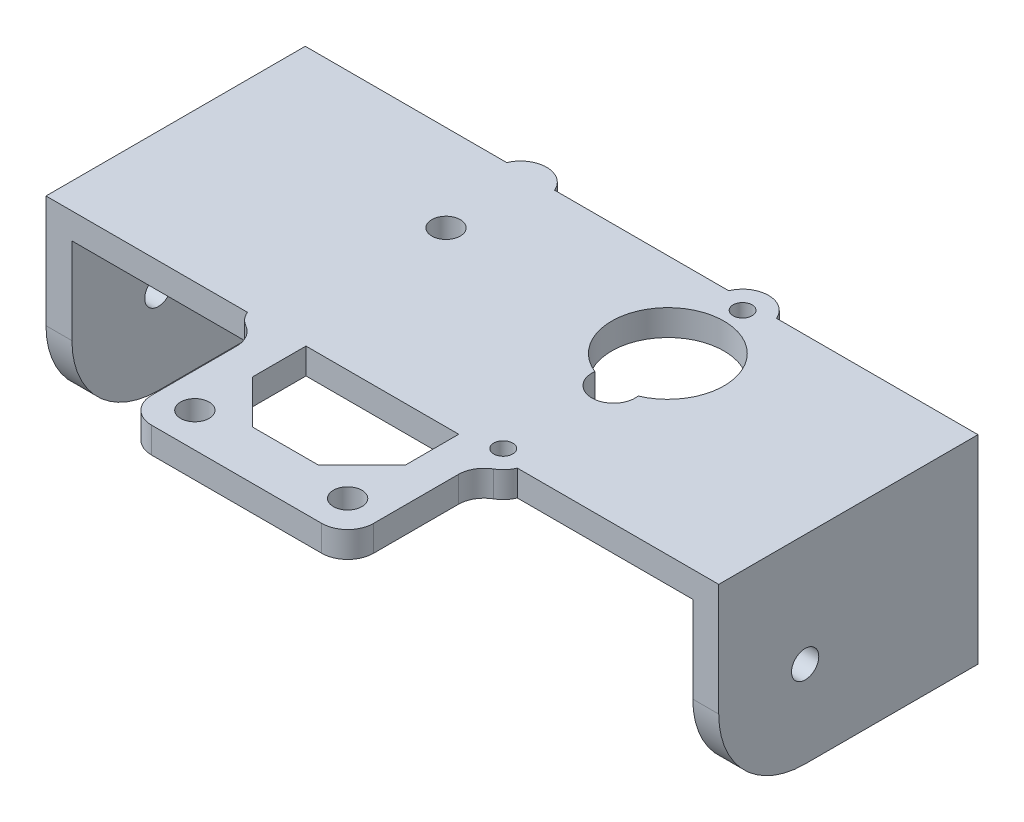
SolidWorks part; units mm, degrees
ref_plane "Front Plane" through (0, 0, 0) normal (0, 0, 1) x (1, 0, 0)
ref_plane "Top Plane" through (0, 0, 0) normal (0, 1, 0) x (1, 0, 0)
ref_plane "Right Plane" through (0, 0, 0) normal (1, 0, 0) x (0, 0, -1)
sketch "Sketch1" plane through (0, 0, 0) normal (0, 0, 1) x (1, 0, 0)
  line L0 (-32.8463, 7.5233) -> (32.9944, 7.5233) construction
  line L2 (-38.8463, 10.5233) -> (38.9944, 10.5233)
  line L3 (-38.8463, 10.5233) -> (-38.8463, 7.5233)
  line L4 (-38.8463, 7.5233) -> (38.9944, 7.5233)
  line L5 (38.9944, 10.5233) -> (38.9944, 7.5233)
  line L6 (-38.8463, 10.5233) -> (38.9944, 7.5233) construction
  line L7 (-38.8463, 7.5233) -> (38.9944, 10.5233) construction
  line L8 (38.9944, 10.5233) -> (35.9944, 10.5233)
  line L10 (-32.8463, 2.523) -> (32.9944, 2.5233) construction
  line L13 (-38.8463, 10.5233) -> (-35.8463, 10.5233)
  line L14 (-38.8463, 10.5233) -> (-38.8463, -12.4767)
  line L15 (-38.8463, -12.4767) -> (-35.8463, -12.4767)
  line L16 (-35.8463, 10.5233) -> (-35.8463, -12.4767)
  line L17 (0.0741, 2.5231) -> (0.0741, -23.3949) construction
  line L18 (38.9944, 10.5233) -> (38.9944, -12.4767)
  line L19 (38.9944, -12.4767) -> (35.9944, -12.4767)
  line L20 (35.9944, 10.5233) -> (35.9944, -12.4767)
  line L21 (-35.8463, -12.4767) -> (-32.8463, -12.4767) construction
  line L22 (32.9944, -12.4767) -> (35.9944, -12.4767) construction
  point P2 (0.2537, 9.0233)
  dimension "D1" = 3
  dimension "D2" = 3
  dimension "D3" = 3
extrude "Boss-Extrude1" add sketch "Sketch1" along normal blind 30 contours L16 L4 L14 L15 | L16 L2 L3 L4 | L20 L2 L16 L4 | L2 L20 L4 L5 | L4 L20 L19 L18 region at (-37.3463, 9.0233, 0) region at (0.0741, 9.0233, 0) region at (-37.3463, -2.4767, 0) region at (37.4944, 9.0233, 0) region at (37.4944, -2.4767, 0)
fillet "Fillet1" radius 10 2 edges at (37.4944, -12.4767, 30) (-37.3463, -12.4767, 30)
sketch "Sketch2" plane through (0, 0, 0) normal (1, 0, 0) x (0, 0, -1)
  line L0 (20, -2.4767) -> (-20, -2.4767) construction
  line L1 (-30, 10.5233) -> (-30, -2.4767) construction
  circle A0 centre (-20, -2.4767) radius 1.575
  dimension "D2" = 3.15
  dimension "D1" = 10
extrude "Cut-Extrude1" cut sketch "Sketch2" against normal mid plane 100
sketch "Sketch3" plane through (0, 10.5233, 0) normal (0, 1, 0) x (1, 0, 0)
  line L0 (0.0741, -30) -> (0, 0) construction
  line L1 (-38.8463, -30) -> (38.9944, -30) construction
  circle A2 centre (12.9136, -9.8077) radius 6.5
  circle A3 centre (12.9886, -16.1672) radius 2.5
  circle A4 centre (12.9136, -1.1577) radius 1.1
  circle A5 centre (12.9136, -28.8577) radius 1.1
  circle A6 centre (-12.508, -10.0504) radius 1.65
  dimension "D2" = 2.2
  dimension "D3" = 3.3
  dimension "D4" = 13
  dimension "D5" = 5
  dimension "D1" = 2.2
extrude "Cut-Extrude2" cut sketch "Sketch3" against normal up to surface (3 mm away) contours A5 | A2 A3 | A2 A3 | A3 A2 | A4 | A6 region at (12.9086, 10.5233, 9.3903) region at (12.976, 10.5233, 15.0994) region at (13.0009, 10.5233, 17.2105) region at (12.9136, 10.5233, 1.1577) region at (12.9136, 10.5233, 28.8577) region at (-12.508, 10.5233, 10.0504) up to face at (0.0741, 7.5233, 15)
sketch "Sketch4" plane through (0, 10.5233, 0) normal (0, 1, 0) x (1, 0, 0)
  line L0 (0.0741, -30) -> (0.0741, 0) construction
  line L1 (-38.8463, -30) -> (38.9944, -30) construction
  line L2 (-38.8463, 0) -> (38.9944, 0) construction
  line L3 (-8.7654, -36.2077) -> (-3.7654, -41.2077)
  line L4 (6.9136, -46.8577) -> (-6.7654, -46.8577)
  line L5 (-8.7654, -30) -> (8.9136, -30)
  line L6 (-8.7654, -30) -> (-8.7654, -36.2077)
  line L7 (6.9136, -46.8577) -> (12.9136, -46.8577)
  line L8 (-3.7654, -41.2077) -> (3.9136, -41.2077)
  line L9 (12.9136, -46.8577) -> (12.9136, -31.8577)
  line L10 (8.9136, -30) -> (8.9136, -36.2077)
  line L11 (3.9136, -41.2077) -> (8.9136, -36.2077)
  line L17 (-6.7654, -46.8577) -> (-12.7654, -46.8577)
  line L18 (-12.7654, -46.8577) -> (-12.7654, -31.8577)
  circle A0 centre (12.9136, -28.8577) radius 3
  circle A1 centre (12.9136, -1.1577) radius 3
  circle A2 centre (-12.7654, -1.1577) radius 3
  circle A3 centre (-12.7654, -28.8577) radius 3
  circle A4 centre (8.9136, -42.8577) radius 1.65
  circle A5 centre (-8.7654, -42.8577) radius 1.65
  point P14 (8.9136, -41.2077)
  point P15 (-8.7654, -41.2077)
  line M5 (38.9944, 0) -> (-38.8463, 0)
  line M7 (-38.8463, -30) -> (38.9944, -30)
  dimension "D1" = 6
  dimension "D2" = 6
  dimension "D4" = 3.3
  dimension "D3" = 15
  dimension "D5" = 4
extrude "Boss-Extrude2" add sketch "Sketch4" against normal up to surface (3 mm away) contours A0 M7 | A1 M5 | A3 L4 A0 M7 | A3 M7 | A2 M5 region at (-6.4827, 10.5233, 38.9249) region at (-12.7654, 10.5233, 30.7672) region at (12.9136, 10.5233, 30.7672) region at (-12.7654, 10.5233, -0.7606) region at (12.9136, 10.5233, -0.7606) up to face at (12.9136, 7.5233, 29.9577)
fillet "Fillet3" radius 3 4 edges at (-12.7654, 9.0233, 46.8577) (-12.7654, 9.0233, 31.8577) (12.9136, 9.0233, 31.8577) (12.9136, 9.0233, 46.8577)
